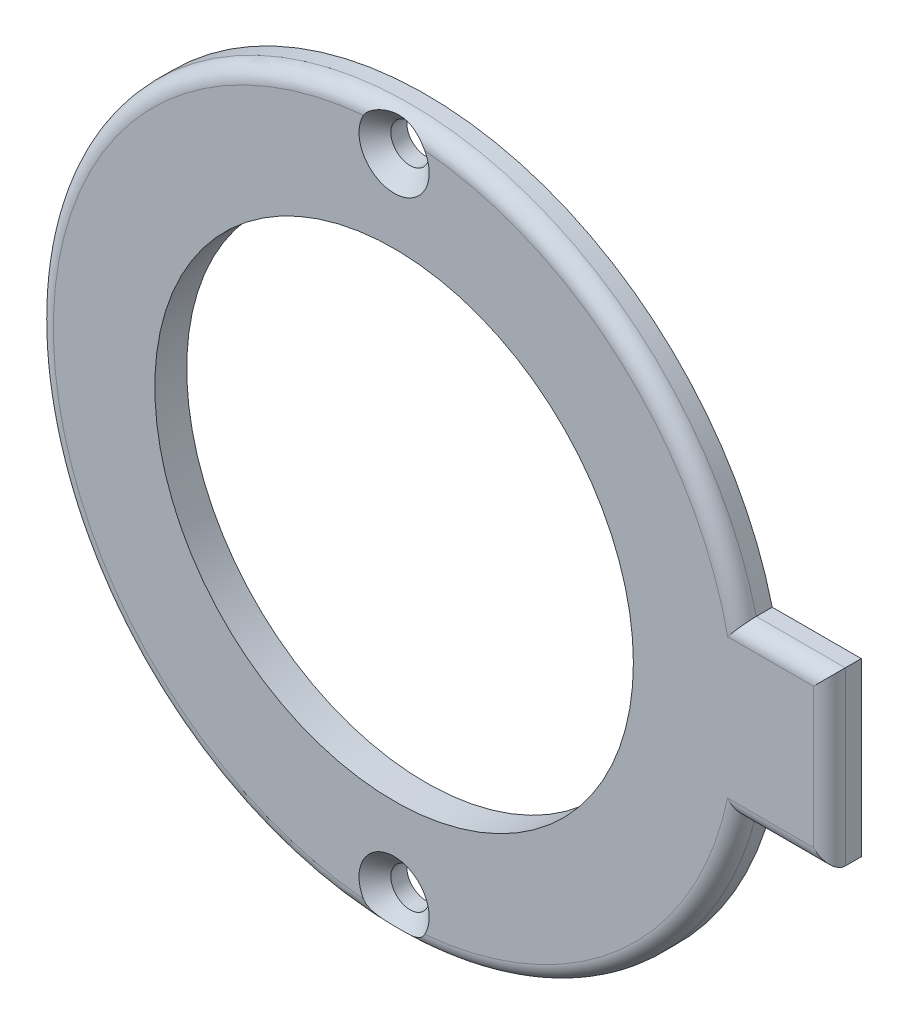
SolidWorks part; units mm, degrees
ref_plane "Piano frontale" through (0, 0, 0) normal (0, 0, 1) x (1, 0, 0)
ref_plane "Piano superiore" through (0, 0, 0) normal (0, 1, 0) x (1, 0, 0)
ref_plane "Piano destro" through (0, 0, 0) normal (1, 0, 0) x (0, 0, -1)
sketch "Schizzo1" plane through (0, 0, 0) normal (0, 0, 1) x (1, 0, 0)
  line L0 (21.7031, -5.38) -> (27.2831, -5.38)
  line L1 (27.2831, -5.38) -> (27.2831, 5.38)
  line L2 (27.2831, 5.38) -> (21.7031, 5.38)
  line L3 (-22.36, 0) -> (38.8398, 0) construction
  arc A0 (21.7031, -5.38) -> (21.7031, 5.38) centre (0, 0) cw
  point P8 (38.8398, 0)
  point P9 (27.2831, 0)
  dimension "D2" = 22.36
  dimension "D1" = 5.58
  dimension "D3" = 10.76
extrude "Estrusione-Estrusione1" add sketch "Schizzo1" along normal blind 2
sketch "Schizzo3" plane through (0, 0, 2) normal (0, 0, 1) x (1, 0, 0)
  circle A0 centre (0, 0) radius 15
  dimension "D1" = 30
extrude "Taglio-Estrusione1" cut sketch "Schizzo3" against normal blind 2
hole_wizard "Foro svasato per Vite M2-1" positions "Schizzo4" profile "Schizzo5" countersink size "M2" standard "ISO"
sketch "Schizzo4" plane through (0, 0, 2) normal (0, 0, 1) x (1, 0, 0)
  line L0 (0, -20.2) -> (0, 22.36) construction
  arc A0 (21.7031, 5.38) -> (21.7031, -5.38) centre (0, 0) ccw construction
  point P0 (0, 20.2)
  point P2 (0, -20.2)
  point P18 (0, 0)
  dimension "D2" = 20.2
  dimension "D1" = 20.2
sketch "Schizzo5" plane through (0, 20.2, 2) normal (1, 0, 0) x (0, -1, 0)
  line L0 (0, 0) -> (0, 60.721)
  line L1 (0, 60.721) -> (1.2, 60)
  line L2 (1.2, 60) -> (1.2, 1)
  line L3 (1.2, 1) -> (2.2, 0)
  line L5 (2.2, 0) -> (0, 0)
  line L6 (-1.2, 1) -> (-2.2, 0) construction
  line L10 (0, 60.721) -> (-1.2, 60) construction
  line L11 (0, -6.35) -> (0, 107.95) construction
  dimension "Hole Dia." = 2.4
  dimension "Hole Depth" = 60
  dimension "Near C'Sink Dia." = 4.4
  dimension "Near C'Sink Angle" = 90
  dimension "Drill Angle" = 118
fillet "Raccordo1" radius 1 4 edges at (24.4931, 5.38, 2) (24.4931, -5.38, 2) (27.2831, 0, 2) (13.9505, -17.4744, 2)
